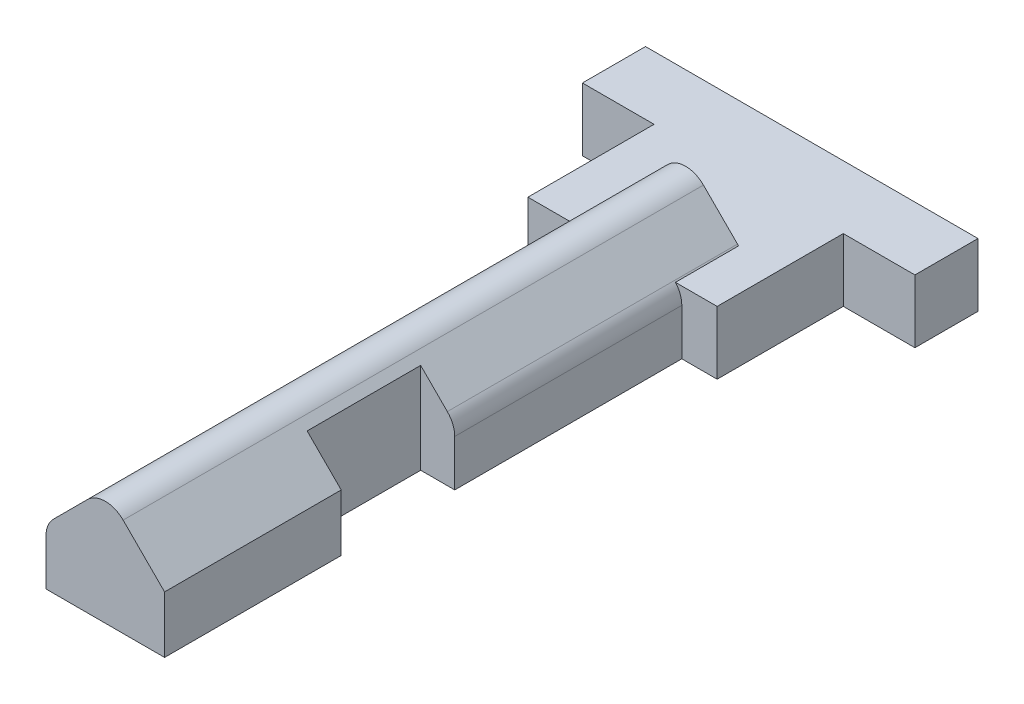
SolidWorks part; units mm, degrees
ref_plane "Płaszczyzna przednia" through (0, 0, 0) normal (0, 0, 1) x (1, 0, 0)
ref_plane "Płaszczyzna górna" through (0, 0, 0) normal (0, 1, 0) x (1, 0, 0)
ref_plane "Płaszczyzna prawa" through (0, 0, 0) normal (1, 0, 0) x (0, 0, -1)
sketch "Szkic1" plane through (0, 0, 0) normal (0, 0, 1) x (1, 0, 0)
  line L0 (0, 0) -> (0, 9.4056) construction
  line L1 (-4.7, 2.25) -> (4.7, 2.25)
  line L2 (-4.7, 2.25) -> (-4.7, -2.25)
  line L3 (-4.7, -2.25) -> (4.7, -2.25)
  line L4 (4.7, 2.25) -> (4.7, -2.25)
  line L5 (-4.7, 2.25) -> (4.7, -2.25) construction
  line L6 (-4.7, -2.25) -> (4.7, 2.25) construction
  line L7 (-4.7, 2.25) -> (0, 6.95)
  line L8 (0, 6.95) -> (4.7, 2.25)
  point P0 (0, 0)
  dimension "D1" = 9.4
  dimension "D2" = 4.5
  dimension "D3" = 45
extrude "Dodanie-wyciągnięcie1" add sketch "Szkic1" along normal blind 46 contours L8 L7 L1 | L4 L1 L2 L3 region at (0, 3.8167, 0) region at (0, 0, 0)
sketch "Szkic2" plane through (0, -2.25, 0) normal (0, -1, 0) x (1, 0, 0)
  line L0 (0, 0) -> (0, 46) construction
  line L1 (-4.7, 0) -> (4.7, 0) construction
  line L2 (-4.7, 46) -> (4.7, 46) construction
  line L3 (2, 32) -> (2, 23)
  line L4 (0, 23) -> (10, 23)
  line L5 (0, 23) -> (0, 32)
  line L6 (0, 32) -> (10, 32)
  line L7 (10, 23) -> (10, 32)
  line M6 (4.7, 0) -> (4.7, 46)
  dimension "D1" = 10
  dimension "D2" = 9
  dimension "D3" = 23
  dimension "D4" = 2
extrude "Wytnij-wyciągnięcie1" cut sketch "Szkic2" against normal blind 10 contours L6 L3 L4 M6 | L4 L7 L6 M6 region at (3.35, -2.25, 27.5) region at (7.35, -2.25, 27.5)
ref_plane "Płaszczyzna1" through (-22.5, 11.75, 5) normal (0, -1, 0) x (-1, 0, 0)
sketch "Szkic4" plane through (0, -2.25, 0) normal (0, -1, 0) x (1, 0, 0)
  line L0 (0, 0) -> (0, 5) construction
  line L2 (-4.7, 0) -> (4.7, 0) construction
  line L3 (0, 0) -> (0, -7.3747) construction
  line L9 (7.5, -5) -> (-7.5, -5)
  line L10 (7.5, -5) -> (7.5, 5)
  line L11 (7.5, 5) -> (-7.5, 5)
  line L12 (-7.5, -5) -> (-7.5, 5)
  line L13 (7.5, -5) -> (-7.5, 5) construction
  line L14 (7.5, 5) -> (-7.5, -5) construction
  line L15 (13.1781, -10) -> (-13.1781, -10)
  line L16 (13.1781, -10) -> (13.1781, -5)
  line L17 (13.1781, -5) -> (-13.1781, -5)
  line L18 (-13.1781, -10) -> (-13.1781, -5)
  line L19 (13.1781, -10) -> (-13.1781, -5) construction
  line L20 (13.1781, -5) -> (-13.1781, -10) construction
  point P4 (0, 0)
  point P10 (0, -7.5)
  line M14 (-4.7, 46) -> (-4.7, 0)
  line M15 (-4.7, 0) -> (4.7, 0)
  line M16 (4.7, 0) -> (4.7, 23)
  dimension "D1" = 5
  dimension "D2" = 15
  dimension "D3" = 10
  dimension "D4" = 5
extrude "Dodanie-wyciągnięcie2" add sketch "Szkic4" against normal blind 5 contours L18 L15 L16 L17 L9 | L12 L9 L10 L11 M16 M15 M14 | L10 L9 L12 L11 region at (0, -2.25, -7.5) region at (0, -2.25, -1.1408)
fillet "Zaokrąglenie1" radius 2 3 edges at (4.7, 2.25, 14) (-4.7, 2.25, 25.5) (0, 6.95, 23)
